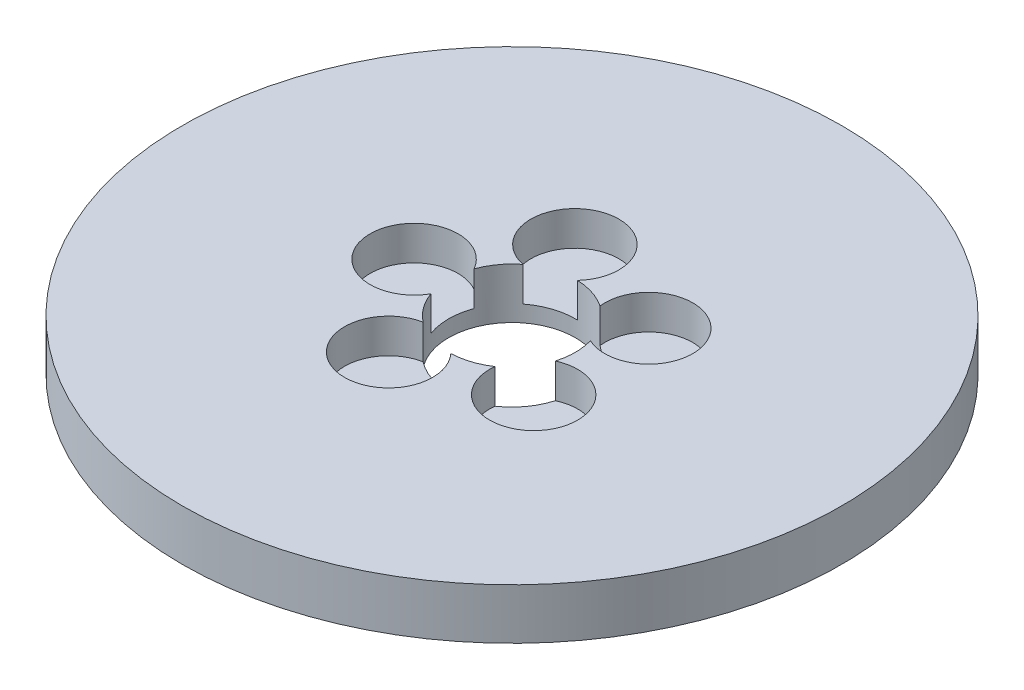
SolidWorks part; units mm, degrees
ref_plane "Front Plane" through (0, 0, 0) normal (0, 0, 1) x (1, 0, 0)
ref_plane "Top Plane" through (0, 0, 0) normal (0, 1, 0) x (1, 0, 0)
ref_plane "Right Plane" through (0, 0, 0) normal (1, 0, 0) x (0, 0, -1)
sketch "Sketch1" plane through (0, 0, 0) normal (0, 1, 0) x (1, 0, 0)
  circle A0 centre (0, 0) radius 65
  dimension "FLANGE_OD" = 130
extrude "Boss-Extrude1" add sketch "Sketch1" along normal blind 10
sketch "Sketch2" plane through (0, 0, 0) normal (0, 1, 0) x (1, 0, 0)
  circle A0 centre (0, 0) radius 12.5
  dimension "BORE_D" = 25
extrude "Cut-Extrude1" cut sketch "Sketch2" along normal through all
sketch "Sketch3" plane through (0, 10, 0) normal (0, 1, 0) x (1, 0, 0)
  circle A0 centre (0, 0) radius 19.312 construction
  circle A1 centre (-19.312, 0) radius 8.6833
  dimension "BOLT_D" = 17.3667
  dimension "BOLT_PCD" = 38.624
extrude "Cut-Extrude2" cut sketch "Sketch3" against normal blind 6.775
pattern_circular "CirPattern1" count 5 over 360 about axis through (0, 0, 0) along (0, 1, 0) of "Cut-Extrude2"
